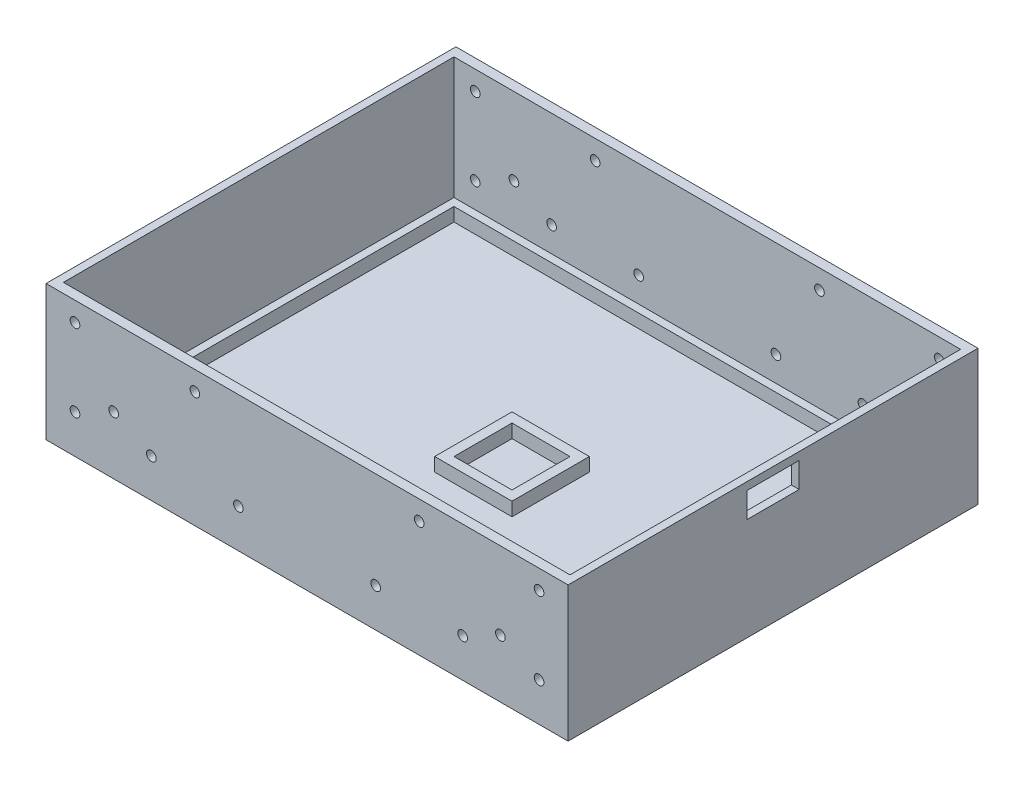
SolidWorks part; units mm, degrees
ref_plane "Front Plane" through (0, 0, 0) normal (0, 0, 1) x (1, 0, 0)
ref_plane "Top Plane" through (0, 0, 0) normal (0, 1, 0) x (1, 0, 0)
ref_plane "Right Plane" through (0, 0, 0) normal (1, 0, 0) x (0, 0, -1)
sketch "Sketch1" plane through (0, 0, 0) normal (0, 1, 0) x (1, 0, 0)
  line L1 (-135, -106) -> (135, -106)
  line L2 (-135, -106) -> (-135, 106)
  line L3 (-135, 106) -> (135, 106)
  line L4 (135, -106) -> (135, 106)
  line L5 (-135, -106) -> (135, 106) construction
  line L6 (-135, 106) -> (135, -106) construction
  point P0 (0, 0)
  dimension "D1" = 270
  dimension "D2" = 212
extrude "Boss-Extrude1" add sketch "Sketch1" along normal blind 10
sketch "Sketch2" plane through (0, 10, 0) normal (0, 1, 0) x (1, 0, 0)
  line L5 (-131, -101) -> (131, -101)
  line L6 (-131, -101) -> (-131, 101)
  line L7 (-131, 101) -> (131, 101)
  line L16 (135, -106) -> (135, 106)
  line L17 (135, 106) -> (-135, 106)
  line L18 (-135, 106) -> (-135, -106)
  line L19 (-135, -106) -> (135, -106)
  line L20 (135, -106) -> (135, 106)
  line L21 (135, 106) -> (-135, 106)
  line L22 (-135, 106) -> (-135, -106)
  line L23 (-135, -106) -> (135, -106)
  line L24 (131, -101) -> (131, 101)
  line L25 (-131, -101) -> (131, 101) construction
  line L26 (-131, 101) -> (131, -101) construction
  point P2 (0, 0)
  dimension "D1" = 262
  dimension "D3" = 202
  dimension "D2" = 0
extrude "Boss-Extrude2" add sketch "Sketch2" along normal blind 70
sketch "Sketch3" plane through (0, 10, 0) normal (0, 1, 0) x (1, 0, 0)
  line L0 (-135, 115) -> (-135, -115)
  line L1 (-135, -115) -> (135, -115)
  line L2 (135, -115) -> (135, 115)
  line L3 (135, 115) -> (-135, 115)
  line L4 (-131, -101) -> (131, -101)
  line L13 (-15, -15) -> (15, -15)
  line L14 (-15, -15) -> (-15, 15)
  line L15 (-15, 15) -> (15, 15)
  line L16 (15, -15) -> (15, 15)
  line L17 (-15, -15) -> (15, 15) construction
  line L18 (-15, 15) -> (15, -15) construction
  line L19 (-20, -20) -> (20, -20)
  line L20 (-20, -20) -> (-20, 20)
  line L21 (-20, 20) -> (20, 20)
  line L22 (20, -20) -> (20, 20)
  line L23 (-20, -20) -> (20, 20) construction
  line L24 (-20, 20) -> (20, -20) construction
  line L28 (-131, -101) -> (131, -101)
  line L32 (131, -101) -> (131, 101)
  line L34 (131, -101) -> (131, 101)
  line L36 (131, 101) -> (-131, 101)
  line L37 (131, 101) -> (-131, 101)
  line L38 (-131, 101) -> (-131, -101)
  line L39 (-131, 101) -> (-131, -101)
  point P8 (0, 0)
  point P14 (0, 0)
  dimension "D3" = 30
  dimension "D4" = 5
  dimension "D1" = 0
extrude "Boss-Extrude3" add sketch "Sketch3" along normal blind 7 contours L19 L22 L21 L20 L16 L13 L14 L15 | L3 L2 L1 L0 region at (-19.4343, 10, 0)
chamfer "Chamfer1" distance 10 angle 45 4 edges at (0, 0, -106) (-135, 0, 0) (0, 0, 106) (135, 0, 0)
sketch "Sketch4" plane through (0, 0, 106) normal (0, 0, 1) x (1, 0, 0)
  line L0 (35.5, 30) -> (80.5, 30) construction
  line L1 (-135, 10) -> (135, 10) construction
  circle A0 centre (80.5, 30) radius 2.5
  circle A1 centre (35.5, 30) radius 2.5
  circle A2 centre (58, 70) radius 2.5
  point P6 (58, 30)
  dimension "D1" = 5
  dimension "D2" = 45
  dimension "D3" = 40
  dimension "D4" = 20
  dimension "D5" = 58
extrude "Cut-Extrude1" cut sketch "Sketch4" against normal up to surface (5 mm away) up to face at (0, 45, 101)
ref_axis "Axis1" through (0, 84, 0) along (0, -1, 0)
pattern_circular "CirPattern1" count 2 over 360 about axis through (0, 84, 0) along (0, -1, 0) of "Cut-Extrude1"
mirror "Mirror2" about plane through (0, 0, 0) normal (1, 0, 0) of "CirPattern1"
sketch "Sketch5" plane through (0, 0, 106) normal (0, 0, 1) x (1, 0, 0)
  line L0 (-135, 10) -> (135, 10) construction
  line L1 (-135, 80) -> (-135, 10) construction
  circle A0 centre (-120, 70) radius 2.5
  circle A1 centre (-120, 30) radius 2.5
  circle A2 centre (-100, 40) radius 2.5
  dimension "D1" = 5
  dimension "D2" = 40
  dimension "D3" = 20
  dimension "D4" = 15
  dimension "D5" = 30
  dimension "D6" = 20
extrude "Cut-Extrude2" cut sketch "Sketch5" against normal through all
mirror "Mirror1" about plane through (0, 0, 0) normal (1, 0, 0) of "Cut-Extrude2"
fillet "Fillet1" radius 7 4 edges at (0, 0, 96) (125, 0, 0) (0, 0, -96) (-125, 0, 0)
sketch "Sketch6" plane through (0, 10, 0) normal (0, 1, 0) x (1, 0, 0)
  line L0 (-127, 97) -> (-127, -97)
  line L1 (-127, -97) -> (127, -97)
  line L2 (127, -97) -> (127, 97)
  line L3 (127, 97) -> (-127, 97)
  line L4 (-131, -101) -> (131, -101)
  line L6 (-131, -101) -> (131, -101)
  line L16 (131, 101) -> (-131, 101)
  line L18 (131, 101) -> (-131, 101)
  line L20 (-131, 101) -> (-131, -101)
  line L21 (-131, 101) -> (-131, -101)
  line L22 (131, -101) -> (131, 101)
  line L23 (131, -101) -> (131, 101)
  point P3 (126.5481, -94.8566)
  point P5 (120.6495, 87.4263)
  point P8 (124.045, 97)
  point P9 (121.3201, 92.7998)
  dimension "D2" = 4
  dimension "D3" = 4
  dimension "D4" = 4
  dimension "D5" = 4
  dimension "D1" = 0
extrude "Boss-Extrude4" add sketch "Sketch6" along normal up to surface (7 mm away) up to face at (0, 17, 0)
sketch "Sketch7" plane through (135, 0, 0) normal (1, 0, 0) x (0, 0, -1)
  line L0 (0, 84) -> (0, -4) construction
  line L1 (-13.5, 76) -> (13.5, 76)
  line L2 (-13.5, 76) -> (-13.5, 63)
  line L3 (-13.5, 63) -> (13.5, 63)
  line L4 (13.5, 76) -> (13.5, 63)
  line L5 (-13.5, 76) -> (13.5, 63) construction
  line L6 (-13.5, 63) -> (13.5, 76) construction
  line L7 (-106, 80) -> (106, 80) construction
  point P0 (0, 69.5)
  dimension "D1" = 27
  dimension "D2" = 13
  dimension "D3" = 4
extrude "Cut-Extrude3" cut sketch "Sketch7" against normal up to surface (4 mm away) up to face at (131, 48.5, 0)
